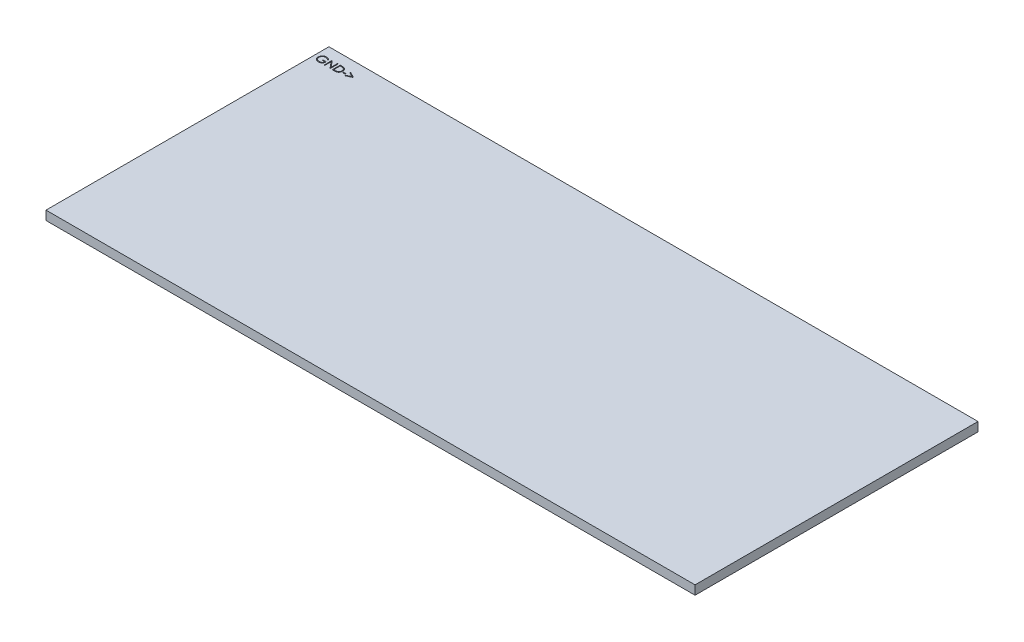
SolidWorks part; units mm, degrees
ref_plane "Front Plane" through (0, 0, 0) normal (0, 0, 1) x (1, 0, 0)
ref_plane "Top Plane" through (0, 0, 0) normal (0, 1, 0) x (1, 0, 0)
ref_plane "Right Plane" through (0, 0, 0) normal (1, 0, 0) x (0, 0, -1)
sketch "Sketch1" plane through (0, 0, 0) normal (0, 1, 0) x (1, 0, 0)
  line L1 (0, 0) -> (114.2, 0)
  line L2 (0, 0) -> (0, 49.784)
  line L3 (0, 49.784) -> (114.2, 49.784)
  line L4 (114.2, 0) -> (114.2, 49.784)
  point P7 (6.858, 47.244)
extrude "Boss-Extrude1" add sketch "Sketch1" along normal blind 1.5875
sketch "Sketch2" plane through (0, 1.5875, 0) normal (0, 1, 0) x (1, 0, 0)
  text T0 "GND->" font "Century Gothic" height 1.4
  point P1 (6.858, 47.244)
extrude "Cut-Extrude1" cut sketch "Sketch2" against normal blind 0.2
sketch "Sketch5" plane through (0, 0, 0) normal (0, -1, 0) x (1, 0, 0)
  line L0 (101.1416, -7.6744) -> (94.742, -7.6744) construction
  text T2 "GND->" font "Century Gothic" height 1.4
  point P6 (0, 0)
  point P7 (94.742, -8.382)
extrude "Cut-Extrude2" cut sketch "Sketch5" against normal blind 0.2
